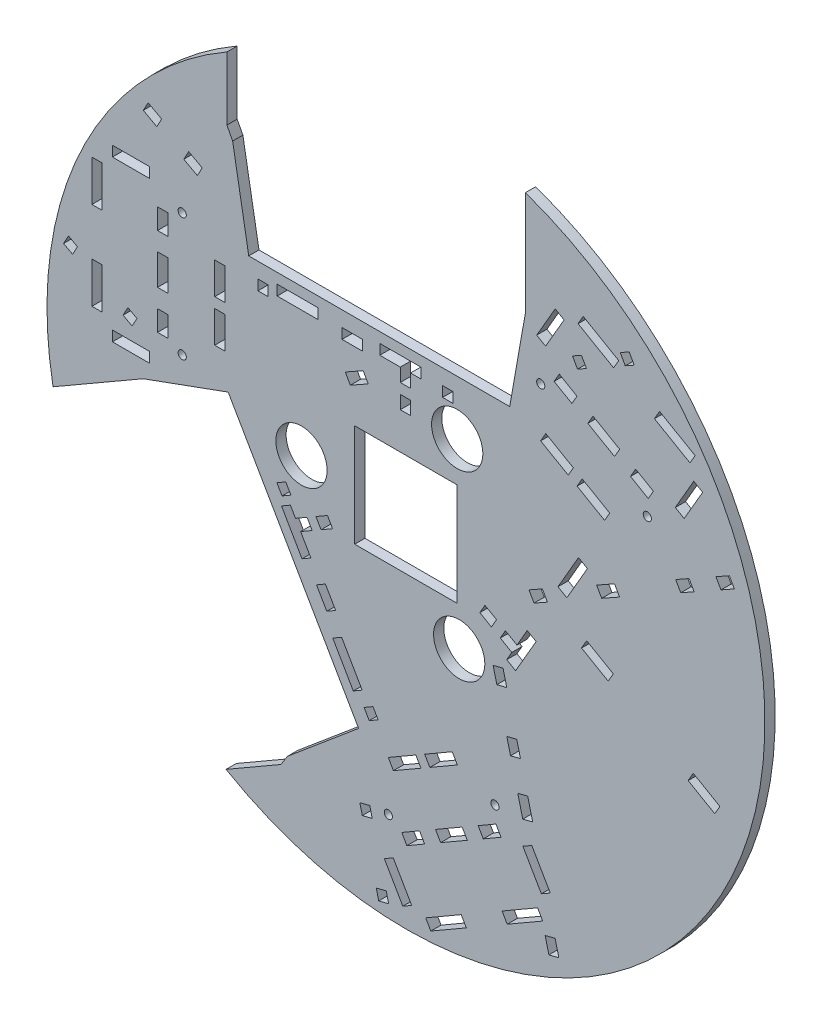
SolidWorks part; units mm, degrees
material "Balsa"
ref_plane "Plan de face" through (0, 0, 0) normal (0, 0, 1) x (1, 0, 0)
ref_plane "Plan de dessus" through (0, 0, 0) normal (0, 1, 0) x (1, 0, 0)
ref_plane "Plan de droite" through (0, 0, 0) normal (1, 0, 0) x (0, 0, -1)
sketch "Esquisse1" plane through (0, 0, 0) normal (0, 0, 1) x (1, 0, 0)
  circle A0 centre (148.0804, -12.1102) radius 175
  dimension "D1" = 350
extrude "Boss.-Extru.1" add sketch "Esquisse1" along normal blind 5
sketch "Esquisse2" plane through (0, 0, 5) normal (0, 0, 1) x (1, 0, 0)
  line L0 (135.3118, 53.7774) -> (135.3118, 48.7774)
  line L1 (5, 72.2774) -> (23, 72.2774)
  line L2 (5, 72.2774) -> (5, 67.2774)
  line L3 (5, 67.2774) -> (23, 67.2774)
  line L4 (23, 72.2774) -> (23, 67.2774)
  line L5 (-5, 62.2774) -> (0, 62.2774)
  line L6 (-5, 62.2774) -> (-5, 42.2774)
  line L7 (-5, 42.2774) -> (0, 42.2774)
  line L8 (0, 62.2774) -> (0, 42.2774)
  line L9 (-5, 19.2774) -> (0, 19.2774)
  line L10 (-5, 19.2774) -> (-5, -0.7226)
  line L11 (-5, -0.7226) -> (0, -0.7226)
  line L12 (0, 19.2774) -> (0, -0.7226)
  line L13 (5, -5.7226) -> (23, -5.7226)
  line L14 (5, -5.7226) -> (5, -10.7226)
  line L15 (5, -10.7226) -> (23, -10.7226)
  line L16 (23, -5.7226) -> (23, -10.7226)
  line L17 (27, 14.2774) -> (32, 14.2774)
  line L18 (27, 14.2774) -> (27, 4.2774)
  line L19 (27, 4.2774) -> (32, 4.2774)
  line L20 (32, 14.2774) -> (32, 4.2774)
  line L21 (27, 38.2774) -> (32, 38.2774)
  line L22 (27, 38.2774) -> (27, 23.2774)
  line L23 (27, 23.2774) -> (32, 23.2774)
  line L24 (32, 38.2774) -> (32, 23.2774)
  line L25 (27, 57.2774) -> (32, 57.2774)
  line L26 (27, 57.2774) -> (27, 47.2774)
  line L27 (27, 47.2774) -> (32, 47.2774)
  line L28 (32, 57.2774) -> (32, 47.2774)
  line L29 (54.86, 48.7774) -> (59.86, 48.7774)
  line L30 (54.86, 48.7774) -> (54.86, 33.2774)
  line L31 (54.86, 33.2774) -> (59.86, 33.2774)
  line L32 (59.86, 48.7774) -> (59.86, 33.2774)
  line L33 (54.86, 28.2774) -> (59.86, 28.2774)
  line L34 (54.86, 28.2774) -> (54.86, 12.7774)
  line L35 (54.86, 12.7774) -> (59.86, 12.7774)
  line L36 (59.86, 28.2774) -> (59.86, 12.7774)
  line L37 (85.3118, 53.7774) -> (105.3118, 53.7774)
  line L38 (85.3118, 53.7774) -> (85.3118, 48.7774)
  line L39 (85.3118, 48.7774) -> (105.3118, 48.7774)
  line L40 (105.3118, 53.7774) -> (105.3118, 48.7774)
  line L41 (145.3118, 37.2774) -> (150.3118, 37.2774)
  line L42 (145.3118, 37.2774) -> (145.3118, 30.7774)
  line L43 (145.3118, 30.7774) -> (150.3118, 30.7774)
  line L44 (150.3118, 37.2774) -> (150.3118, 30.7774)
  line L45 (135.3118, 48.7774) -> (145.3118, 48.7774)
  line L46 (155.3118, 48.7774) -> (135.3118, 48.7774) construction
  line L47 (145.3118, 48.7774) -> (145.3118, 42.2774)
  line L48 (145.3118, 42.2774) -> (150.3118, 42.2774)
  line L49 (150.3118, 42.2774) -> (150.3118, 48.7774)
  line L50 (150.3118, 48.7774) -> (155.3118, 48.7774)
  line L51 (155.3118, 48.7774) -> (155.3118, 53.7774)
  line L52 (155.3118, 53.7774) -> (135.3118, 53.7774)
  line L53 (292.7025, 69.6073) -> (283.7025, 54.0188)
  line L54 (292.7025, 69.6073) -> (288.3723, 72.1073)
  line L55 (288.3723, 72.1073) -> (279.3723, 56.5188)
  line L56 (283.7025, 54.0188) -> (279.3723, 56.5188)
  line L57 (289.0422, 83.2676) -> (286.5422, 78.9374)
  line L58 (289.0422, 83.2676) -> (271.7217, 93.2676)
  line L59 (271.7217, 93.2676) -> (269.2217, 88.9374)
  line L60 (286.5422, 78.9374) -> (269.2217, 88.9374)
  line L61 (251.8031, 104.7676) -> (249.3031, 100.4374)
  line L62 (251.8031, 104.7676) -> (234.4826, 114.7676)
  line L63 (234.4826, 114.7676) -> (231.9826, 110.4374)
  line L64 (249.3031, 100.4374) -> (231.9826, 110.4374)
  line L65 (225.1525, 108.6073) -> (216.1525, 93.0188)
  line L66 (225.1525, 108.6073) -> (220.8223, 111.1073)
  line L67 (220.8223, 111.1073) -> (211.8223, 95.5188)
  line L68 (216.1525, 93.0188) -> (211.8223, 95.5188)
  line L69 (231.473, 79.5547) -> (228.973, 75.2246)
  line L70 (231.473, 79.5547) -> (222.8127, 84.5547)
  line L71 (222.8127, 84.5547) -> (220.3127, 80.2246)
  line L72 (228.973, 75.2246) -> (220.3127, 80.2246)
  line L73 (252.2576, 67.5547) -> (249.7576, 63.2246)
  line L74 (252.2576, 67.5547) -> (239.2672, 75.0547)
  line L75 (239.2672, 75.0547) -> (236.7672, 70.7246)
  line L76 (249.7576, 63.2246) -> (236.7672, 70.7246)
  line L77 (268.7121, 58.0547) -> (266.2121, 53.7246)
  line L78 (268.7121, 58.0547) -> (260.0518, 63.0547)
  line L79 (260.0518, 63.0547) -> (257.5518, 58.7246)
  line L80 (266.2121, 53.7246) -> (257.5518, 58.7246)
  line L81 (247.4209, 38.1773) -> (244.9209, 33.8472)
  line L82 (247.4209, 38.1773) -> (233.9975, 45.9273)
  line L83 (233.9975, 45.9273) -> (231.4975, 41.5972)
  line L84 (244.9209, 33.8472) -> (231.4975, 41.5972)
  line L85 (229.6673, 48.4273) -> (227.1673, 44.0972)
  line L86 (229.6673, 48.4273) -> (216.2439, 56.1773)
  line L87 (216.2439, 56.1773) -> (213.7439, 51.8472)
  line L88 (227.1673, 44.0972) -> (213.7439, 51.8472)
  line L89 (211.5251, -33.996) -> (207.195, -31.496)
  line L90 (236.5251, 9.3053) -> (226.5251, -8.0153)
  line L91 (236.5251, 9.3053) -> (232.195, 11.8053)
  line L92 (232.195, 11.8053) -> (222.195, -5.5153)
  line L93 (226.5251, -8.0153) -> (222.195, -5.5153)
  line L94 (192.2357, -34.4063) -> (189.7357, -38.7364)
  line L95 (192.2357, -34.4063) -> (186.6065, -31.1563)
  line L96 (186.6065, -31.1563) -> (184.1065, -35.4864)
  line L97 (189.7357, -38.7364) -> (184.1065, -35.4864)
  line L98 (207.195, -31.496) -> (202.195, -40.1563)
  line L99 (202.195, -40.1563) -> (196.5658, -36.9063)
  line L100 (196.5658, -36.9063) -> (194.0658, -41.2364)
  line L101 (194.0658, -41.2364) -> (199.695, -44.4864)
  line L102 (199.695, -44.4864) -> (197.195, -48.8165)
  line L103 (197.195, -48.8165) -> (201.5251, -51.3165)
  line L104 (201.5251, -51.3165) -> (211.5251, -33.996)
  line L105 (146.5388, -178.2153) -> (137.5388, -162.6268)
  line L106 (146.5388, -178.2153) -> (150.869, -175.7153)
  line L107 (150.869, -175.7153) -> (141.869, -160.1268)
  line L108 (137.5388, -162.6268) -> (141.869, -160.1268)
  line L109 (160.1991, -181.8755) -> (157.6991, -177.5454)
  line L110 (160.1991, -181.8755) -> (177.5196, -171.8755)
  line L111 (177.5196, -171.8755) -> (175.0196, -167.5454)
  line L112 (157.6991, -177.5454) -> (175.0196, -167.5454)
  line L113 (197.4382, -160.3755) -> (194.9382, -156.0454)
  line L114 (197.4382, -160.3755) -> (214.7587, -150.3755)
  line L115 (214.7587, -150.3755) -> (212.2587, -146.0454)
  line L116 (194.9382, -156.0454) -> (212.2587, -146.0454)
  line L117 (214.0888, -139.2153) -> (205.0888, -123.6268)
  line L118 (214.0888, -139.2153) -> (218.4189, -136.7153)
  line L119 (218.4189, -136.7153) -> (209.4189, -121.1268)
  line L120 (205.0888, -123.6268) -> (209.4189, -121.1268)
  line L121 (185.7683, -130.1627) -> (183.2683, -125.8326)
  line L122 (185.7683, -130.1627) -> (194.4286, -125.1627)
  line L123 (194.4286, -125.1627) -> (191.9286, -120.8326)
  line L124 (183.2683, -125.8326) -> (191.9286, -120.8326)
  line L125 (164.9837, -142.1627) -> (162.4837, -137.8326)
  line L126 (164.9837, -142.1627) -> (177.9741, -134.6627)
  line L127 (177.9741, -134.6627) -> (175.4741, -130.3326)
  line L128 (162.4837, -137.8326) -> (175.4741, -130.3326)
  line L129 (148.5292, -151.6627) -> (146.0292, -147.3326)
  line L130 (148.5292, -151.6627) -> (157.1895, -146.6627)
  line L131 (157.1895, -146.6627) -> (154.6895, -142.3326)
  line L132 (146.0292, -147.3326) -> (154.6895, -142.3326)
  line L133 (141.9604, -123.2852) -> (139.4604, -118.9551)
  line L134 (141.9604, -123.2852) -> (155.3838, -115.5352)
  line L135 (155.3838, -115.5352) -> (152.8838, -111.2051)
  line L136 (139.4604, -118.9551) -> (152.8838, -111.2051)
  line L137 (159.7139, -113.0352) -> (157.2139, -108.7051)
  line L138 (159.7139, -113.0352) -> (173.1373, -105.2852)
  line L139 (173.1373, -105.2852) -> (170.6373, -100.9551)
  line L140 (157.2139, -108.7051) -> (170.6373, -100.9551)
  line L141 (97.4044, -56.1119) -> (101.7345, -53.6119)
  line L142 (122.4044, -99.4132) -> (112.4044, -82.0927)
  line L143 (122.4044, -99.4132) -> (126.7345, -96.9132)
  line L144 (126.7345, -96.9132) -> (116.7345, -79.5927)
  line L145 (112.4044, -82.0927) -> (116.7345, -79.5927)
  line L146 (106.6938, -39.2017) -> (104.1938, -34.8716)
  line L147 (106.6938, -39.2017) -> (112.323, -35.9517)
  line L148 (112.323, -35.9517) -> (109.823, -31.6216)
  line L149 (104.1938, -34.8716) -> (109.823, -31.6216)
  line L150 (101.7345, -53.6119) -> (96.7345, -44.9517)
  line L151 (96.7345, -44.9517) -> (102.3637, -41.7017)
  line L152 (102.3637, -41.7017) -> (99.8637, -37.3716)
  line L153 (99.8637, -37.3716) -> (94.2345, -40.6216)
  line L154 (94.2345, -40.6216) -> (91.7345, -36.2914)
  line L155 (91.7345, -36.2914) -> (87.4044, -38.7914)
  line L156 (87.4044, -38.7914) -> (97.4044, -56.1119)
  line L157 (135.3118, 53.7774) -> (135.3118, 48.7774) construction
  line L158 (105.3118, 53.7774) -> (135.3118, 53.7774) construction
  point P83 (148.0804, -12.1102)
  point P192 (148.0804, -12.1102)
  point P193 (148.0804, -12.1102)
  dimension "D1" = 3
extrude "Enlèv. mat.-Extru.1" cut sketch "Esquisse2" against normal blind 5
sketch "Esquisse6" plane through (0, 0, 5) normal (0, 0, 1) x (1, 0, 0)
  line L0 (93.9998, -7.2151) -> (100.2998, -18.127) construction
  line L1 (206.3213, 102.2219) -> (206.3213, 185.5637)
  line L2 (123.0804, -37.1102) -> (173.0804, -37.1102)
  line L3 (123.0804, -37.1102) -> (123.0804, 12.8898)
  line L4 (123.0804, 12.8898) -> (173.0804, 12.8898)
  line L5 (173.0804, -37.1102) -> (173.0804, 12.8898)
  line L6 (123.0804, -37.1102) -> (173.0804, 12.8898) construction
  line L7 (123.0804, 12.8898) -> (173.0804, -37.1102) construction
  line L8 (206.3213, 185.5637) -> (60.7972, 185.5637)
  line L9 (71.4438, 58.7774) -> (63.5848, 103.3483)
  line L10 (71.4438, 58.7774) -> (198.6608, 58.7774)
  line L11 (198.6608, 58.7774) -> (206.3213, 102.2219)
  line L12 (60.7972, 185.5637) -> (60.7972, 108.6824)
  line L13 (19.9456, -18.8381) -> (-52.2306, -60.5091)
  line L14 (-52.2306, -60.5091) -> (20.5314, -186.5366)
  line L15 (63.5848, 103.3483) -> (60.7972, 108.6824)
  line L16 (125.0083, -113.9232) -> (90.3383, -143.0148)
  line L17 (125.0083, -113.9232) -> (61.3998, -3.7501)
  line L18 (61.3998, -3.7501) -> (19.9456, -18.8381)
  line L20 (236.1714, -21.3074) -> (249.1617, -28.8074)
  line L21 (236.1714, -21.3074) -> (233.6714, -25.6375)
  line L22 (249.1617, -28.8074) -> (246.6617, -33.1375)
  line L23 (233.6714, -25.6375) -> (246.6617, -33.1375)
  line L24 (288.1329, -51.3074) -> (301.1233, -58.8074)
  line L25 (288.1329, -51.3074) -> (285.6329, -55.6375)
  line L26 (301.1233, -58.8074) -> (298.6233, -63.1375)
  line L27 (285.6329, -55.6375) -> (298.6233, -63.1375)
  line L28 (226.5251, -8.0153) -> (236.5251, 9.3053) construction
  line L29 (279.3723, 56.5188) -> (283.7025, 54.0188) construction
  line L31 (64.5427, 103.6743) -> (63.0102, 106.6067) construction
  line L32 (20.5314, -186.5366) -> (87.1126, -148.0959)
  line L33 (90.3383, -143.0148) -> (87.1126, -148.0959)
  circle A0 centre (173.06, 32.2774) radius 12.5
  circle A1 centre (174.0314, -55.9369) radius 12.5
  circle A2 centre (97.1498, -12.671) radius 12.5
  point P2 (148.0804, -12.1102)
  point P8 (148.0804, -12.1102)
  point P10 (148.0804, -12.1102)
  point P35 (148.0804, -12.1102)
  point P48 (148.0804, -12.1102)
  dimension "D12" = 25
  dimension "D3" = 50
  dimension "D4" = 50
  dimension "D5" = 70.8876
  dimension "D6" = 50.5804
  dimension "D7" = 127.217
  dimension "D8" = 100
  dimension "D9" = 100
  dimension "D10" = 145.5241
  dimension "D11" = 43.4444
  dimension "D13" = 5
  dimension "D14" = 15
  dimension "D15" = 15
  dimension "D16" = 45
  dimension "D17" = 15
  dimension "D18" = 89
  dimension "D19" = 2
  dimension "D20" = 1
  dimension "D1" = 3
extrude "Enlèv. mat.-Extru.6" cut sketch "Esquisse6" against normal blind 5
hole_wizard "Trous de centrage Ø4.0mm1" positions "Esquisse7" profile "Esquisse8" hole size "Ø4.0" standard "Ansi Metric" end condition through all
sketch "Esquisse7" plane through (148.0804, -12.1102, -78) normal (0, 0, -1) x (1, 0, 0)
  point P0 (65.7012, -88.0226)
  point P3 (117.6627, -58.0226)
  point P6 (-109.0804, -72.8876)
  point P9 (-109.0804, -12.8876)
  point P12 (-8.5823, 130.9102)
  point P15 (43.3792, 100.9102)
sketch "Esquisse8" plane through (213.7816, 75.9124, -78) normal (1, 0, 0) x (0, 1, 0)
  line L0 (0, 0) -> (0, 83)
  line L1 (0, 83) -> (2, 83)
  line L2 (2, 83) -> (2, 0)
  line L3 (2, 0) -> (0, 0)
  line L4 (0, -6.35) -> (0, 107.95) construction
  dimension "Diamètre du perçage jusqu'au prochain" = 4
  dimension "Profondeur du perçage jusqu'au prochain" = 83
sketch "Esquisse9" plane through (0, 0, 5) normal (0, 0, 1) x (1, 0, 0)
  line L0 (301.6473, 32.8747) -> (299.2005, 37.2351)
  line L1 (301.6473, 32.8747) -> (308.1879, 36.5449)
  line L2 (299.2005, 37.2351) -> (305.7411, 40.9053)
  line L3 (308.1879, 36.5449) -> (305.7411, 40.9053)
  line L4 (282.0254, 21.8642) -> (279.5786, 26.2246)
  line L5 (282.0254, 21.8642) -> (288.566, 25.5344)
  line L6 (279.5786, 26.2246) -> (286.1192, 29.8948)
  line L7 (288.566, 25.5344) -> (286.1192, 29.8948)
  line L8 (252.2089, 5.133) -> (249.7621, 9.4935)
  line L9 (252.2089, 5.133) -> (243.488, 0.2395)
  line L10 (249.7621, 9.4935) -> (241.0412, 4.5999)
  line L11 (243.488, 0.2395) -> (241.0412, 4.5999)
  line L12 (214.6084, -10.2326) -> (217.0552, -14.593)
  line L13 (214.6084, -10.2326) -> (208.0678, -13.9027)
  line L14 (217.0552, -14.593) -> (210.5146, -18.2632)
  line L15 (208.0678, -13.9027) -> (210.5146, -18.2632)
  line L16 (217.0552, -14.593) -> (243.488, 0.2395) construction
  line L17 (214.6084, -10.2326) -> (217.0552, -14.593) construction
  line L18 (259.3473, 106.6065) -> (254.9869, 104.1597)
  line L19 (259.3473, 106.6065) -> (256.9005, 110.9669)
  line L20 (254.9869, 104.1597) -> (252.5401, 108.5201)
  line L21 (256.9005, 110.9669) -> (252.5401, 108.5201)
  line L22 (236.0696, 93.5445) -> (231.7091, 91.0977)
  line L23 (236.0696, 93.5445) -> (233.6228, 97.9049)
  line L24 (231.7091, 91.0977) -> (229.2624, 95.4581)
  line L25 (233.6228, 97.9049) -> (229.2624, 95.4581)
  line L26 (129.6754, 33.8428) -> (120.9546, 28.9492)
  line L27 (129.6754, 33.8428) -> (127.2286, 38.2032)
  line L28 (120.9546, 28.9492) -> (118.5078, 33.3096)
  line L29 (127.2286, 38.2032) -> (118.5078, 33.3096)
  line L30 (259.3473, 106.6065) -> (120.9546, 28.9492) construction
  line L31 (301.6473, 32.8747) -> (217.0552, -14.593) construction
  line L32 (-16.4384, 23.2791) -> (-12.0459, 20.8904)
  line L33 (-16.4384, 23.2791) -> (-18.8272, 18.8866)
  line L34 (-12.0459, 20.8904) -> (-14.4347, 16.4979)
  line L35 (-18.8272, 18.8866) -> (-14.4347, 16.4979)
  line L36 (12.552, 7.5136) -> (16.9445, 5.1249)
  line L37 (12.552, 7.5136) -> (10.1633, 3.1211)
  line L38 (16.9445, 5.1249) -> (14.5558, 0.7324)
  line L39 (10.1633, 3.1211) -> (14.5558, 0.7324)
  line L42 (-26.9196, -12.1102) -> (148.0804, -12.1102) construction
  line L44 (22.4127, 98.9071) -> (29.0015, 95.324)
  line L45 (22.4127, 98.9071) -> (20.024, 94.5146)
  line L46 (29.0015, 95.324) -> (26.6128, 90.9315)
  line L47 (20.024, 94.5146) -> (26.6128, 90.9315)
  line L48 (42.179, 88.1579) -> (48.7677, 84.5748)
  line L49 (42.179, 88.1579) -> (39.7903, 83.7654)
  line L50 (48.7677, 84.5748) -> (46.379, 80.1823)
  line L51 (39.7903, 83.7654) -> (46.379, 80.1823)
  line L53 (148.0804, -12.1102) -> (9.6568, -109.2191) construction
  line L55 (129.7636, 187.6323) -> (148.0804, -12.1102) construction
  arc A0 (60.3638, -163.5394) -> (206.3213, 152.9141) centre (148.0804, -12.1102) ccw construction
  line B0 (154.106, -73.5915) -> (185.6214, -199.5155) construction
  line B1 (126.7996, -149.8343) -> (125.5857, -144.9839)
  line B2 (130.4361, -143.77) -> (125.5857, -144.9839)
  line B3 (131.65, -148.6204) -> (126.7996, -149.8343)
  line B4 (131.65, -148.6204) -> (130.4361, -143.77)
  line B5 (134.8115, -181.8469) -> (133.5976, -176.9965)
  line B6 (138.448, -175.7826) -> (133.5976, -176.9965)
  line B7 (139.6619, -180.633) -> (134.8115, -181.8469)
  line B8 (139.6619, -180.633) -> (138.448, -175.7826)
  line B9 (190.562, -54.5014) -> (195.4124, -53.2875)
  line B10 (197.2333, -60.5631) -> (195.4124, -53.2875)
  line B11 (192.3829, -61.777) -> (190.562, -54.5014)
  line B12 (192.3829, -61.777) -> (197.2333, -60.5631)
  line B13 (202.089, -79.9647) -> (197.2386, -81.1786)
  line B14 (199.0595, -88.4542) -> (197.2386, -81.1786)
  line B15 (203.9099, -87.2403) -> (202.089, -79.9647)
  line B16 (203.9099, -87.2403) -> (199.0595, -88.4542)
  line B17 (222.6043, -161.9364) -> (217.7539, -163.1503)
  line B18 (215.933, -155.8747) -> (217.7539, -163.1503)
  line B19 (220.7834, -154.6608) -> (222.6043, -161.9364)
  line B20 (220.7834, -154.6608) -> (215.933, -155.8747)
  dimension "D9" = 170.2546
  dimension "D1" = 10
  dimension "D2" = 5
  dimension "D3" = 7.5
  dimension "D4" = 10
  dimension "D5" = 7.5
  dimension "D6" = 7.5
  dimension "D7" = 5
  dimension "D8" = 117
  dimension "D10" = 167.3371
  dimension "D11" = 69
  dimension "D12" = 35.051
  dimension "D13" = 30.31
  dimension "D14" = 5
sketch_block_instance "Bloc1-1"
sketch_block "Bloc1"
extrude "Holes catchers of glass" cut sketch "Esquisse9" against normal blind 10
sketch "Esquisse10" plane through (0, 0, 5) normal (0, 0, 1) x (1, 0, 0)
  line L0 (89.4961, -27.6144) -> (91.9961, -31.9445)
  line L1 (89.4961, -27.6144) -> (85.1672, -30.1137)
  line L2 (91.9961, -31.9445) -> (87.6672, -34.4438)
  line L3 (85.1672, -30.1137) -> (87.6672, -34.4438)
  dimension "D1" = 4.9986
extrude "Holes boards servo" cut sketch "Esquisse10" against normal blind 10
sketch "Esquisse11" plane through (0, 0, 5) normal (0, 0, 1) x (1, 0, 0)
  line L0 (109.4829, -72.2325) -> (104.4829, -63.5722)
  line L1 (109.4829, -72.2325) -> (113.813, -69.7325)
  line L2 (104.4829, -63.5722) -> (108.813, -61.0722)
  line L3 (113.813, -69.7325) -> (108.813, -61.0722)
  line L4 (125.166, -99.3964) -> (108.8992, -71.2215) construction
  line L6 (116.7345, -79.5927) -> (112.4044, -82.0927) construction
  line L7 (130.166, -108.0567) -> (134.4961, -105.5567)
  line L8 (130.166, -108.0567) -> (127.666, -103.7266)
  line L9 (134.4961, -105.5567) -> (131.9961, -101.2266)
  line L10 (127.666, -103.7266) -> (131.9961, -101.2266)
  line L11 (207.4302, -101.3064) -> (209.8581, -111.0072)
  line L12 (170.9253, 51.2774) -> (165.9253, 51.2774)
  line L13 (170.9253, 51.2774) -> (170.9253, 46.2774)
  line L14 (170.9253, 46.2774) -> (165.9253, 46.2774)
  line L15 (165.9253, 51.2774) -> (165.9253, 46.2774)
  line L16 (126.9253, 51.2774) -> (116.9253, 51.2774)
  line L17 (126.9253, 51.2774) -> (126.9253, 46.2774)
  line L18 (126.9253, 46.2774) -> (116.9253, 46.2774)
  line L19 (116.9253, 51.2774) -> (116.9253, 46.2774)
  line L20 (80.9253, 51.2774) -> (75.9253, 51.2774)
  line L21 (80.9253, 51.2774) -> (80.9253, 46.2774)
  line L22 (80.9253, 46.2774) -> (75.9253, 46.2774)
  line L23 (75.9253, 51.2774) -> (75.9253, 46.2774)
  line L24 (207.4302, -101.3064) -> (202.5798, -102.5203)
  line L25 (209.8581, -111.0072) -> (205.0077, -112.2211)
  line L26 (202.5798, -102.5203) -> (205.0077, -112.2211)
  line L27 (203.9099, -87.2403) -> (202.089, -79.9647) construction
  line L28 (220.7834, -154.6608) -> (215.933, -155.8747) construction
  dimension "D1" = 10
  dimension "D2" = 10
  dimension "D3" = 5
  dimension "D4" = 5
  dimension "D5" = 5
  dimension "D6" = 10
  dimension "D7" = 45
extrude "Enlèv. mat.-Extru.7" cut sketch "Esquisse11" against normal blind 5
